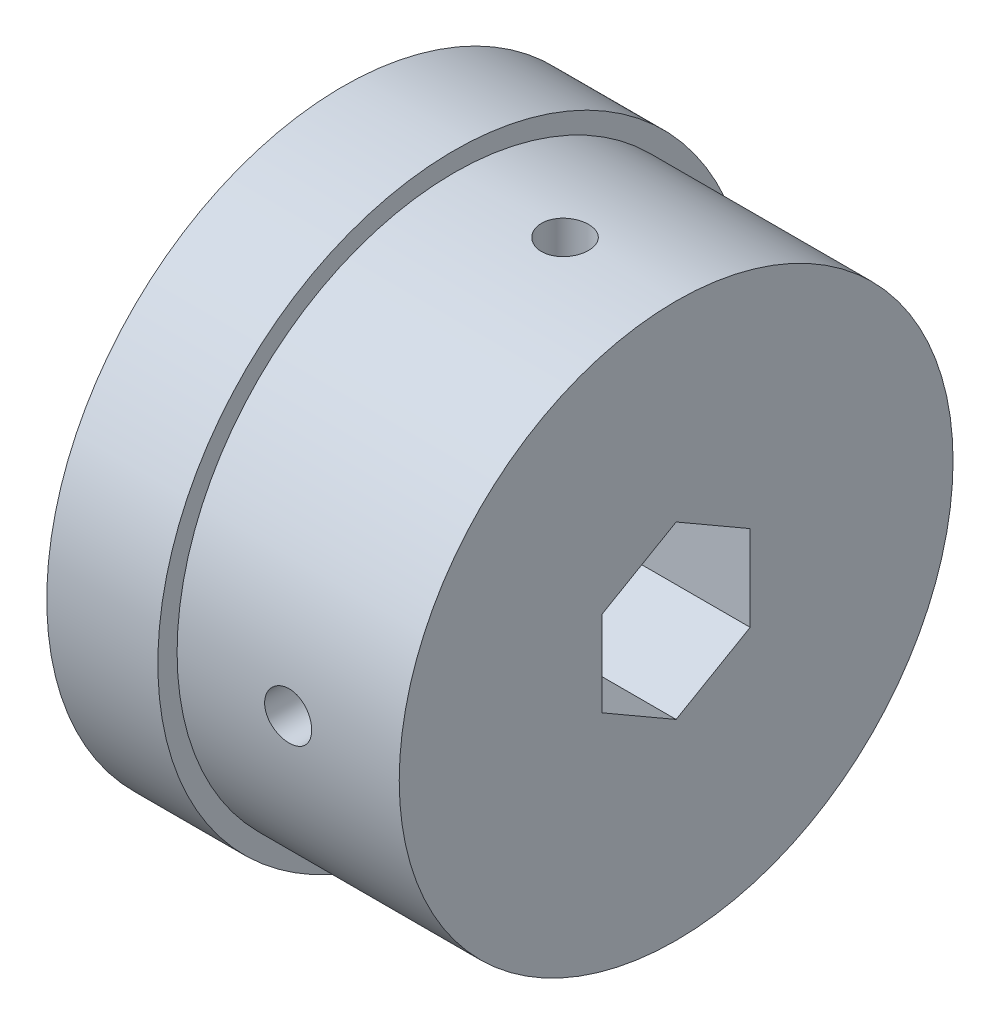
SolidWorks part; units mm, degrees
material "6061-T6 (SS)"
ref_plane "Front Plane" through (0, 0, 0) normal (0, 0, 1) x (1, 0, 0)
ref_plane "Top Plane" through (0, 0, 0) normal (0, 1, 0) x (1, 0, 0)
ref_plane "Right Plane" through (0, 0, 0) normal (1, 0, 0) x (0, 0, -1)
sketch "Sketch1" plane through (0, 0, 0) normal (1, 0, 0) x (0, 0, -1)
  circle A0 centre (0, 0) radius 23.749
  dimension "D1" = 47.498
extrude "Boss-Extrude1" add sketch "Sketch1" along normal blind 19.05
sketch "Sketch2" plane through (0, 0, 0) normal (-1, 0, 0) x (0, 0, 1)
  circle A0 centre (0, 0) radius 25.4
  dimension "D1" = 50.8
extrude "Boss-Extrude2" add sketch "Sketch2" along normal blind 9.525
sketch "Sketch3" plane through (-9.525, 0, 0) normal (-1, 0, 0) x (0, 0, 1)
  circle A0 centre (0, 0) radius 14.2875
  dimension "D1" = 28.575
sketch "Sketch4" plane through (-9.525, 0, 0) normal (-1, 0, 0) x (0, 0, 1)
  line L1 (0, 7.3323) -> (-6.35, 3.6662)
  line L2 (-6.35, 3.6662) -> (-6.35, -3.6662)
  line L3 (-6.35, -3.6662) -> (0, -7.3323)
  line L4 (0, -7.3323) -> (6.35, -3.6662)
  line L5 (6.35, -3.6662) -> (6.35, 3.6662)
  line L6 (6.35, 3.6662) -> (0, 7.3323)
  circle A0 centre (0, 0) radius 6.35 construction
  dimension "D1" = 12.7
extrude "Cut-Extrude1" cut sketch "Sketch4" against normal through all
sketch "Sketch6" plane through (0, 0, 0) normal (0, 0, 1) x (1, 0, 0)
  circle A0 centre (9.525, 0) radius 2.0193
  dimension "D1" = 4.0386
  dimension "D2" = 9.525
extrude "Cut-Extrude3" cut sketch "Sketch6" against normal through all both and the other way through all
sketch "Sketch12" plane through (0, 0, 0) normal (0, 1, 0) x (1, 0, 0)
  circle A0 centre (9.525, 0) radius 2.0193
  dimension "D1" = 4.0386
  dimension "D2" = 9.525
extrude "Cut-Extrude5" cut sketch "Sketch12" against normal through all both and the other way through all
sketch "Sketch7" plane through (19.05, 0, 0) normal (1, 0, 0) x (0, 0, -1)
  line L0 (-4.7625, -12.7) -> (-4.7625, -17.399)
  line L5 (12.7, 4.7625) -> (17.399, 4.7625)
  line L6 (12.7, 4.7625) -> (12.7, -4.7625)
  line L7 (12.7, -4.7625) -> (17.399, -4.7625)
  line L8 (17.399, 4.7625) -> (17.399, -4.7625)
  line L17 (4.7625, -17.399) -> (-4.7625, -17.399)
  line L18 (4.7625, -12.7) -> (4.7625, -17.399)
  line L19 (4.7625, -12.7) -> (-4.7625, -12.7)
  line L20 (-12.7, 4.7625) -> (-17.399, 4.7625)
  line L21 (-17.399, -4.7625) -> (-17.399, 4.7625)
  line L22 (-12.7, -4.7625) -> (-17.399, -4.7625)
  line L23 (-12.7, -4.7625) -> (-12.7, 4.7625)
  line L24 (4.7625, 12.7) -> (4.7625, 17.399)
  line L25 (-4.7625, 17.399) -> (4.7625, 17.399)
  line L26 (-4.7625, 12.7) -> (-4.7625, 17.399)
  line L27 (-4.7625, 12.7) -> (4.7625, 12.7)
  point P16 (17.399, 0)
  point P21 (0, 0)
  dimension "D1" = 9.525
  dimension "D2" = 4.699
  dimension "D3" = 12.7
  dimension "D4" = 4
